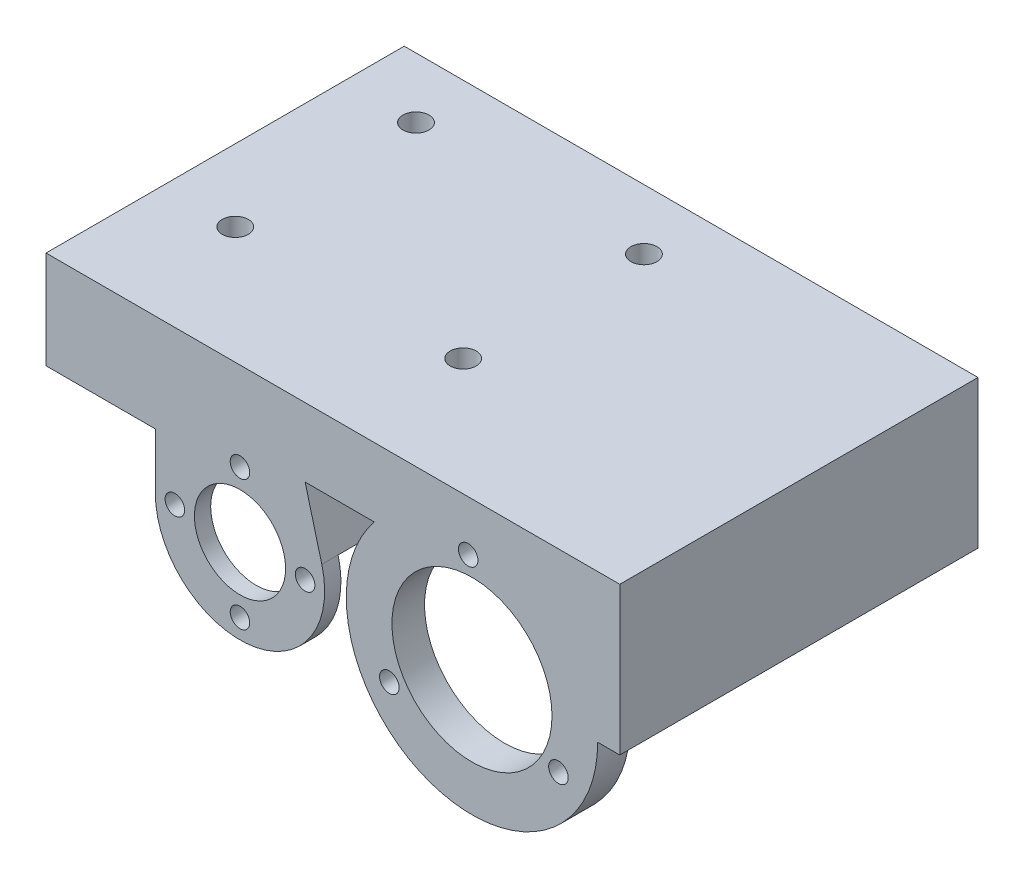
SolidWorks part; units mm, degrees
note: The reader was unsure of these and kept them because the rebuilt part matched: shared geometry of "Sketch1<4>", "Sketch1<5>", "Sketch1<6>", "Sketch2<3>".
ref_plane "Front Plane" through (0, 0, 0) normal (0, 0, 1) x (1, 0, 0)
ref_plane "Top Plane" through (0, 0, 0) normal (0, 1, 0) x (1, 0, 0)
ref_plane "Right Plane" through (0, 0, 0) normal (1, 0, 0) x (0, 0, -1)
sketch "Sketch1" plane through (0, 0, 0) normal (0, 0, 1) x (1, 0, 0)
  line L0 (-225.05, -11.8) -> (-313.144, -11.8)
  line L1 (-100, -11.8) -> (-350, -11.8) construction
  line L2 (-313.144, -26.8) -> (-313.144, -11.8)
  line L3 (-313.144, -26.8) -> (-293.144, -26.8)
  line L5 (-225.05, -11.8) -> (-225.05, -16.8)
  line L6 (-225.05, -16.8) -> (-240.05, -16.8)
  line L7 (-335, -11.8) -> (-225, -11.8) construction
  line L8 (-225.05, -34.5008) -> (-225.05, -16.8)
  line L9 (-262.7468, -22.3619) -> (-283.3617, -22.3619)
  line L10 (-270.7966, -32.0273) -> (-273.3617, -22.3619)
  line L11 (-296.3617, -35.3619) -> (-296.3617, -26.8)
  line L12 (-225.05, -34.5008) -> (-228.4422, -34.5008)
  circle A0 centre (-247.7422, -34.5008) radius 12.2862
  circle A1 centre (-247.7422, -34.5008) radius 19.3
  circle A2 centre (-283.3617, -35.3619) radius 7
  circle A4 centre (-247.7422, -34.5008) radius 19.3 construction
  circle A6 centre (-283.3617, -35.3619) radius 7 construction
  circle A7 centre (-234.4699, -41.4898) radius 1.5
  circle A8 centre (-260.431, -42.5005) radius 1.5
  circle A9 centre (-248.3257, -19.5122) radius 1.5
  circle A10 centre (-260.431, -42.5005) radius 1.5 construction
  circle A11 centre (-234.4699, -41.4898) radius 1.5 construction
  circle A12 centre (-248.3257, -19.5122) radius 1.5 construction
  circle A13 centre (-247.7422, -34.5008) radius 3
  circle A14 centre (-247.7422, -34.5008) radius 3 construction
  circle A15 centre (-273.3617, -35.3619) radius 1.5
  circle A16 centre (-283.3617, -45.3619) radius 1.5
  circle A17 centre (-293.3617, -35.3619) radius 1.5
  circle A18 centre (-283.3617, -25.3619) radius 1.5
  circle A19 centre (-273.3617, -35.3619) radius 1 construction
  circle A20 centre (-283.3617, -45.3619) radius 1 construction
  circle A21 centre (-293.3617, -35.3619) radius 1 construction
  circle A22 centre (-283.3617, -25.3619) radius 1 construction
  arc A23 (-267.0422, -34.5008) -> (-240.05, -16.8) centre (-247.7422, -34.5008) cw
  circle A25 centre (-283.3617, -35.3619) radius 13
  circle A26 centre (-283.3617, -35.3619) radius 13 construction
  dimension "D3" = 3
  dimension "D4" = 3
  dimension "D5" = 3
  dimension "D6" = 3
  dimension "D1" = 5
  dimension "D2" = 15
  dimension "D7" = 15
  dimension "D8" = 20
extrude "Boss-Extrude1" add sketch "Sketch1" against normal up to surface (5 mm away)
extrude "Boss-Extrude2" add sketch "Sketch1<4>" against normal up to surface (5 mm away)
sketch "Sketch1<4>" plane through (0, 0, 0) normal (0, 0, 1) x (1, 0, 0) same geometry as "Sketch1"
extrude "Boss-Extrude3" add sketch "Sketch1<5>" against normal up to surface (2.5 mm away) contours A25 A18 A17 A16 A15 A2
sketch "Sketch1<5>" plane through (0, 0, 0) normal (0, 0, 1) x (1, 0, 0) same geometry as "Sketch1"
extrude "Boss-Extrude4" add sketch "Sketch1<6>" against normal blind 55
sketch "Sketch1<6>" plane through (0, 0, 0) normal (0, 0, 1) x (1, 0, 0) same geometry as "Sketch1"
sketch "Sketch2" plane through (0, -11.8, 0) normal (0, 1, 0) x (1, 0, 0)
  line L1 (-300.0694, 42.25) -> (-298.0487, 45.75)
  line L2 (-298.0487, 45.75) -> (-300.0694, 49.25)
  line L3 (-300.0694, 49.25) -> (-304.1109, 49.25)
  line L4 (-304.1109, 49.25) -> (-306.1316, 45.75)
  line L5 (-306.1316, 45.75) -> (-304.1109, 42.25)
  line L6 (-304.1109, 42.25) -> (-300.0694, 42.25)
  line L7 (-300.0694, 14.5) -> (-298.0487, 18)
  line L8 (-298.0487, 18) -> (-300.0694, 21.5)
  line L9 (-300.0694, 21.5) -> (-304.1109, 21.5)
  line L10 (-304.1109, 21.5) -> (-306.1316, 18)
  line L11 (-306.1316, 18) -> (-304.1109, 14.5)
  line L12 (-304.1109, 14.5) -> (-300.0694, 14.5)
  line L13 (-269.1109, 21.5) -> (-271.1316, 18)
  line L14 (-271.1316, 18) -> (-269.1109, 14.5)
  line L15 (-269.1109, 14.5) -> (-265.0694, 14.5)
  line L16 (-265.0694, 14.5) -> (-263.0487, 18)
  line L17 (-263.0487, 18) -> (-265.0694, 21.5)
  line L18 (-265.0694, 21.5) -> (-269.1109, 21.5)
  line L19 (-269.1109, 42.25) -> (-265.0694, 42.25)
  line L20 (-265.0694, 42.25) -> (-263.0487, 45.75)
  line L21 (-263.0487, 45.75) -> (-265.0694, 49.25)
  line L22 (-265.0694, 49.25) -> (-269.1109, 49.25)
  line L23 (-269.1109, 49.25) -> (-271.1316, 45.75)
  line L24 (-271.1316, 45.75) -> (-269.1109, 42.25)
  circle A0 centre (-302.0902, 45.75) radius 2
  circle A1 centre (-302.0902, 18) radius 2
  circle A2 centre (-267.0902, 45.75) radius 2
  circle A3 centre (-267.0902, 18) radius 2
  circle A4 centre (-302.0902, 45.75) radius 3.5 construction
  circle A5 centre (-302.0902, 18) radius 3.5 construction
  circle A6 centre (-267.0902, 18) radius 3.5 construction
  circle A7 centre (-267.0902, 45.75) radius 3.5 construction
  dimension "D1" = 7
  dimension "D2" = 7
  dimension "D3" = 7
  dimension "D4" = 7
extrude "Cut-Extrude1" cut sketch "Sketch2" against normal through all contours A0 | A1 | A3 | A2
extrude "Cut-Extrude2" cut sketch "Sketch2<3>" along normal blind 8 from surface at -15 starting at face at (-302.0902, -26.8, -20)
sketch "Sketch2<3>" plane through (0, -11.8, 0) normal (0, 1, 0) x (1, 0, 0) same geometry as "Sketch2"
